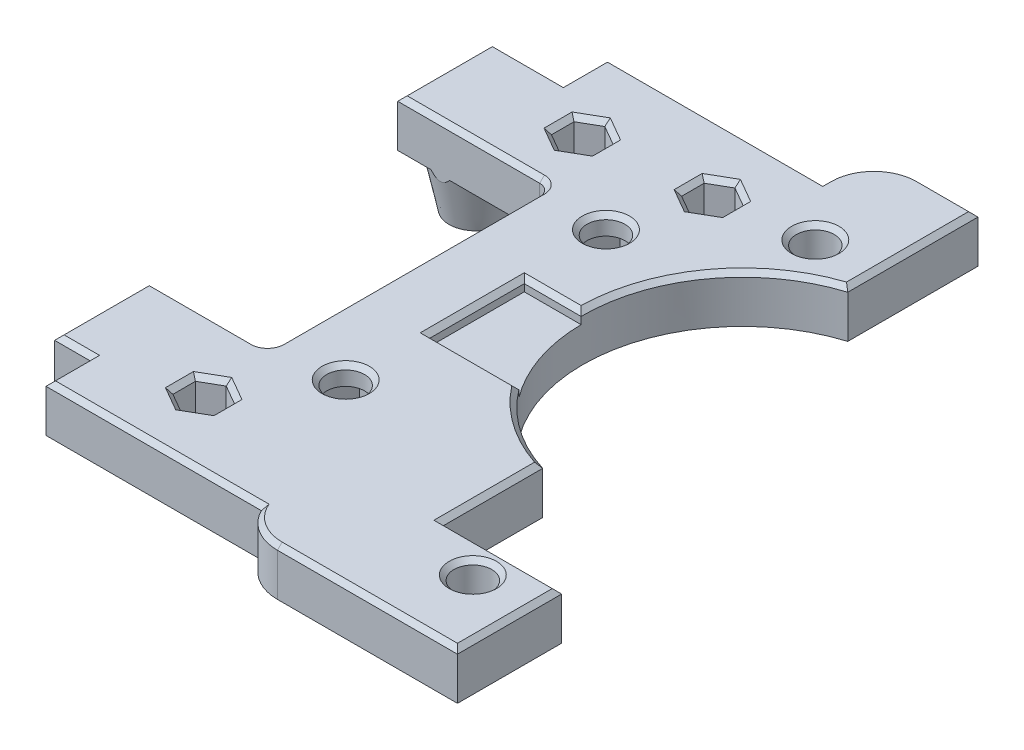
SolidWorks part; units mm, degrees
ref_plane "前视基准面" through (0, 0, 0) normal (0, 0, 1) x (1, 0, 0)
ref_plane "上视基准面" through (0, 0, 0) normal (0, 1, 0) x (1, 0, 0)
ref_plane "右视基准面" through (0, 0, 0) normal (1, 0, 0) x (0, 0, -1)
other "Configuration Table"
sketch "草图1" plane through (0, 0, 0) normal (0, 1, 0) x (1, 0, 0)
  line L1 (0, 0) -> (20, 0)
  line L2 (0, 0) -> (0, 35.74)
  line L3 (0, 35.74) -> (20, 35.74)
  line L4 (20, 0) -> (20, 35.74)
  dimension "D1" = 35.74
  dimension "D2" = 20
extrude "凸台-拉伸1" add sketch "草图1" along normal blind 4
sketch "草图2" plane through (0, 0, 0) normal (0, -1, 0) x (1, 0, 0)
  line L0 (20, 0) -> (20, -35.74) construction
  line L1 (20, 0) -> (11.2, 0)
  line L2 (20, 0) -> (20, 8.08)
  line L3 (20, 8.08) -> (11.2, 8.08)
  line L4 (11.2, 0) -> (11.2, 8.08)
  line L5 (20, -35.74) -> (0, -35.74) construction
  line L6 (20, -35.74) -> (11.2, -35.74)
  line L7 (20, -35.74) -> (20, -45.92)
  line L8 (20, -45.92) -> (11.2, -45.92)
  line L9 (11.2, -35.74) -> (11.2, -45.92)
  line L10 (0, 0) -> (20, 0) construction
  dimension "D1" = 8.8
  dimension "D2" = 8.8
  dimension "D3" = 8.08
  dimension "D4" = 0
  dimension "D5" = 10.18
extrude "凸台-拉伸2" add sketch "草图2" against normal blind 4
sketch "草图3" plane through (0, 0, 0) normal (0, -1, 0) x (-1, 0, 0)
  line L0 (-20, -8.08) -> (-11.2, -8.08) construction
  line L1 (-20, -8.08) -> (-20, 45.92) construction
  circle A0 centre (-24, 22.02) radius 13.5
  dimension "D3" = 27
  dimension "D1" = 30.1
  dimension "D2" = 4
extrude "切除-拉伸1" cut sketch "草图3" against normal blind 10
sketch "草图4" plane through (0, 0, 0) normal (0, -1, 0) x (-1, 0, 0)
  line L1 (-18, 2.17) -> (-9, 2.17)
  line L2 (-18, 2.17) -> (-18, -2.83)
  line L3 (-18, -2.83) -> (-9, -2.83)
  line L4 (-9, 2.17) -> (-9, -2.83)
  line L7 (-20, -8.08) -> (-11.2, -8.08) construction
  line L8 (-20, -8.08) -> (-20, 9.1262) construction
  dimension "D1" = 5
  dimension "D2" = 9
  dimension "D3" = 5.25
  dimension "D4" = 2
extrude "切除-拉伸2" cut sketch "草图4" against normal blind 1
sketch "草图5" plane through (20, 0, 0) normal (1, 0, 0) x (0, 0, -1)
  line L0 (-8.08, 4) -> (-8.08, 0) construction
  line L1 (-8.08, 0) -> (0.729, 0)
  line L2 (-8.08, 0) -> (-8.08, 4)
  line L3 (-8.08, 4) -> (0.729, 4)
  line L4 (0.729, 0) -> (0.729, 4)
  line L5 (-8.08, 0) -> (9.1262, 0) construction
  line L6 (-8.08, 4) -> (9.1262, 4) construction
extrude "凸台-拉伸3" add sketch "草图5" along normal blind 10
sketch "草图6" plane through (0, 0, 0) normal (0, -1, 0) x (-1, 0, 0)
  line L0 (-11.2, 35.74) -> (-11.2, 45.92) construction
  line L1 (-11.2, 45.92) -> (-20, 45.92) construction
  line L2 (-30, -8.08) -> (-11.2, -8.08) construction
  line L3 (-11.2, -8.08) -> (-11.2, -2.83) construction
  circle A0 centre (-15.2, 36.97) radius 1.6
  circle A1 centre (-25.25, -2.03) radius 1.6
  dimension "D1" = 4
  dimension "D2" = 8.95
  dimension "D3" = 3.2
  dimension "D4" = 6.05
  dimension "D5" = 14.05
  dimension "D6" = 3.2
extrude "切除-拉伸3" cut sketch "草图6" against normal blind 10
sketch "草图7" plane through (0, 0, 0) normal (0, -1, 0) x (-1, 0, 0)
  line L0 (0, 35.74) -> (0, 0) construction
  line L1 (-11.2, 35.74) -> (0, 35.74) construction
  circle A0 centre (-5.6, 28.87) radius 1.6
  circle A1 centre (-5.6, 6.87) radius 1.6
  point P6 (0, 17.87)
  point P9 (-5.6, 35.74)
  dimension "D1" = 3.2
  dimension "D2" = 3.2
  dimension "D3" = 11
  dimension "D4" = 11
  dimension "D5" = 0
  dimension "D6" = 0
extrude "切除-拉伸4" cut sketch "草图7" against normal through all
sketch "草图8" plane through (0, 0, 0) normal (0, -1, 0) x (1, 0, 0)
  line L0 (11.2, -35.74) -> (11.2, -45.92) construction
  line L1 (0, -35.74) -> (11.2, -35.74)
  line L2 (0, -35.74) -> (0, -39.74)
  line L3 (0, -39.74) -> (11.2, -39.74)
  line L4 (11.2, -35.74) -> (11.2, -39.74)
  line L5 (11.2, 8.08) -> (11.2, 2.83) construction
  line L6 (0, 0) -> (11.2, 0)
  line L7 (0, 0) -> (0, 4)
  line L8 (0, 4) -> (11.2, 4)
  line L9 (11.2, 0) -> (11.2, 4)
  dimension "D1" = 4
  dimension "D2" = 4
extrude "凸台-拉伸4" add sketch "草图8" against normal up to surface (4 mm away) up to face at (5.6, 4, -30.47)
sketch "草图9" plane through (0, 0, 0) normal (0, -1, 0) x (-1, 0, 0)
  circle A0 centre (-7.6, 35.87) radius 1.65
  circle A1 centre (-0.6, -0.13) radius 1.65
  circle A2 centre (-5.6, 6.87) radius 1.6 construction
  circle A3 centre (-5.6, 28.87) radius 1.6 construction
  dimension "D1" = 3.3
  dimension "D2" = 3.3
  dimension "D3" = 7
  dimension "D4" = 7
  dimension "D5" = 2
  dimension "D6" = 5
extrude "切除-拉伸5" cut sketch "草图9" against normal through all
sketch "草图10" plane through (0, 0, 0) normal (-1, 0, 0) x (0, 0, 1)
  line L0 (-39.74, 0) -> (-45.92, 0) construction
  line L1 (-39.74, 0) -> (-29.87, 0)
  line L2 (-39.74, 0) -> (-39.74, 4)
  line L3 (-39.74, 4) -> (-29.87, 4)
  line L4 (-29.87, 0) -> (-29.87, 4)
  line L5 (-39.74, 4) -> (-39.74, 0) construction
  line L6 (-39.74, 4) -> (-1.407, 4) construction
  line L7 (-39.74, 0) -> (-1.407, 0) construction
  line L8 (4, 4) -> (-5.87, 4)
  line L9 (4, 4) -> (4, 0)
  line L10 (4, 0) -> (-5.87, 0)
  line L11 (-5.87, 4) -> (-5.87, 0)
  dimension "D1" = 9.87
  dimension "D2" = 9.87
extrude "凸台-拉伸5" add sketch "草图10" along normal blind 7
sketch "草图11" plane through (0, 0, 0) normal (0, -1, 0) x (-1, 0, 0)
  circle A0 centre (2.4, 34.87) radius 1.65
  circle A1 centre (-7.6, 35.87) radius 1.65 construction
  dimension "D1" = 3.3
  dimension "D2" = 10
  dimension "D3" = 1
extrude "切除-拉伸6" cut sketch "草图11" against normal blind 8
sketch "草图12" plane through (0, 0, 0) normal (0, -1, 0) x (-1, 0, 0)
  line L1 (-11.2, -2.83) -> (-4.6, -2.83)
  line L2 (-11.2, -2.83) -> (-11.2, 1.75)
  line L3 (-11.2, 1.75) -> (-4.6, 1.75)
  line L4 (-4.6, -2.83) -> (-4.6, 1.75)
  dimension "D1" = 6.6
extrude "切除-拉伸7" cut sketch "草图12" against normal up to surface (1 mm away) up to face at (12.7333, 1, 0.22)
sketch "草图13" plane through (0, 0, 0) normal (0, -1, 0) x (-1, 0, 0)
  circle A0 centre (-0.6, -0.13) radius 1.65
  arc A1 (0, 1.407) -> (0, -1.667) centre (-0.6, -0.13) ccw construction
  dimension "D1" = 0
extrude "切除-拉伸8" cut sketch "草图13" against normal blind 5
sketch "草图14" plane through (0, 0, 0) normal (0, -1, 0) x (-1, 0, 0)
  line L0 (-11.2, -8.08) -> (-11.2, -4) construction
  line L1 (7, -4) -> (-11.2, -4)
  line L2 (7, -4) -> (7, -5.86)
  line L3 (7, -5.86) -> (-11.2, -5.86)
  line L4 (-11.2, -4) -> (-11.2, -5.86)
  line L5 (-11.2, 39.74) -> (-11.2, 45.92) construction
  line L6 (7, 39.74) -> (-11.2, 39.74)
  line L7 (7, 39.74) -> (7, 41.6)
  line L8 (7, 41.6) -> (-11.2, 41.6)
  line L9 (-11.2, 39.74) -> (-11.2, 41.6)
  dimension "D1" = 1.86
  dimension "D2" = 1.86
extrude "凸台-拉伸6" add sketch "草图14" against normal up to surface (4 mm away) up to face at (-2.4, 4, -36.52)
sketch "草图16" plane through (0, 4, 0) normal (0, 1, 0) x (1, 0, 0)
  line L0 (0, 29.87) -> (0, 5.87) construction
  line L1 (5.7, 13.87) -> (15.7, 13.87)
  line L2 (5.7, 13.87) -> (5.7, 21.87)
  line L3 (5.7, 21.87) -> (15.7, 21.87)
  line L4 (15.7, 13.87) -> (15.7, 21.87)
  point P4 (5.7, 17.87)
  point P7 (0, 17.87)
  dimension "D1" = 8
  dimension "D2" = 0
  dimension "D3" = 10
  dimension "D4" = 5.7
extrude "切除-拉伸9" cut sketch "草图16" against normal blind 1
sketch "草图17" plane through (0, 0, 0) normal (0, -1, 0) x (-1, 0, 0)
  line L1 (-8.8332, 28.87) -> (-7.2166, 26.07)
  line L2 (-7.2166, 26.07) -> (-3.9834, 26.07)
  line L3 (-3.9834, 26.07) -> (-2.3668, 28.87)
  line L4 (-2.3668, 28.87) -> (-3.9834, 31.67)
  line L5 (-3.9834, 31.67) -> (-7.2166, 31.67)
  line L6 (-7.2166, 31.67) -> (-8.8332, 28.87)
  line L7 (-8.8332, 6.87) -> (-7.2166, 4.07)
  line L8 (-7.2166, 4.07) -> (-3.9834, 4.07)
  line L9 (-3.9834, 4.07) -> (-2.3668, 6.87)
  line L10 (-2.3668, 6.87) -> (-3.9834, 9.67)
  line L11 (-3.9834, 9.67) -> (-7.2166, 9.67)
  line L12 (-7.2166, 9.67) -> (-8.8332, 6.87)
  circle A0 centre (-5.6, 28.87) radius 2.8 construction
  circle A1 centre (-5.6, 6.87) radius 2.8 construction
  dimension "D1" = 5.6
  dimension "D2" = 5.6
extrude "切除-拉伸10" cut sketch "草图17" against normal blind 2.4
fillet "圆角1" radius 4 2 edges at (11.2, 2, 8.08) (11.2, 2, -45.92)
sketch "草图19" plane through (0, 4, 0) normal (0, 1, 0) x (1, 0, 0)
  line L1 (0.6, -2.0353) -> (2.25, -1.0826)
  line L2 (2.25, -1.0826) -> (2.25, 0.8226)
  line L3 (2.25, 0.8226) -> (0.6, 1.7753)
  line L4 (0.6, 1.7753) -> (-1.05, 0.8226)
  line L5 (-1.05, 0.8226) -> (-1.05, -1.0826)
  line L6 (-1.05, -1.0826) -> (0.6, -2.0353)
  line L7 (-2.4, 32.9647) -> (-0.75, 33.9174)
  line L8 (-0.75, 33.9174) -> (-0.75, 35.8226)
  line L9 (-0.75, 35.8226) -> (-2.4, 36.7753)
  line L10 (-2.4, 36.7753) -> (-4.05, 35.8226)
  line L11 (-4.05, 35.8226) -> (-4.05, 33.9174)
  line L12 (-4.05, 33.9174) -> (-2.4, 32.9647)
  line L13 (7.6, 33.9647) -> (9.25, 34.9174)
  line L14 (9.25, 34.9174) -> (9.25, 36.8226)
  line L15 (9.25, 36.8226) -> (7.6, 37.7753)
  line L16 (7.6, 37.7753) -> (5.95, 36.8226)
  line L17 (5.95, 36.8226) -> (5.95, 34.9174)
  line L18 (5.95, 34.9174) -> (7.6, 33.9647)
  circle A0 centre (0.6, -0.13) radius 1.65 construction
  circle A1 centre (-2.4, 34.87) radius 1.65 construction
  circle A2 centre (7.6, 35.87) radius 1.65 construction
  circle A4 centre (0.6, -0.13) radius 1.65 construction
  circle A5 centre (-2.4, 34.87) radius 1.65 construction
  circle A6 centre (7.6, 35.87) radius 1.65 construction
  dimension "D1" = 0
  dimension "D2" = 0
  dimension "D3" = 0
extrude "切除-拉伸11" cut sketch "草图19" against normal through all
fillet "圆角2" radius 1 2 edges at (0, 2, -5.87) (0, 2, -29.87)
sketch "草图20" plane through (0, 4, 0) normal (0, 1, 0) x (1, 0, 0)
  line L0 (-7, 29.87) -> (-7, 41.6) construction
  line L1 (-7, 37.87) -> (-13, 37.87)
  line L2 (-7, 37.87) -> (-7, 29.87)
  line L3 (-7, 29.87) -> (-13, 29.87)
  line L4 (-13, 37.87) -> (-13, 29.87)
  line L5 (-7, -5.86) -> (-7, 5.87) construction
  line L6 (-7, -2.13) -> (-10, -2.13)
  line L7 (-7, -2.13) -> (-7, 5.87)
  line L8 (-7, 5.87) -> (-10, 5.87)
  line L9 (-10, -2.13) -> (-10, 5.87)
  line L10 (-7, 29.87) -> (-1, 29.87) construction
  line L11 (-7, 5.87) -> (-1, 5.87) construction
  dimension "D1" = 0
  dimension "D2" = 0
  dimension "D3" = 8
  dimension "D4" = 8
  dimension "D5" = 3
  dimension "D6" = 6
extrude "凸台-拉伸7" add sketch "草图20" against normal up to surface (4 mm away) up to face at (0.6, 0, 0.13)
sketch "草图21" plane through (0, 0, 0) normal (0, -1, 0) x (-1, 0, 0)
  line L0 (4.05, 35.8226) -> (4.05, 33.9174) construction
  line L1 (1.05, 0.8226) -> (1.05, -1.0826) construction
  circle A0 centre (6.4, 2.87) radius 2.1
  circle A1 centre (9.4, 32.87) radius 2.1
  point P8 (4.05, 34.87)
  point P11 (1.05, -0.13)
  dimension "D1" = 7
  dimension "D2" = 7
  dimension "D4" = 3
  dimension "D5" = 4.2
  dimension "D6" = 4.2
  dimension "D3" = 2
extrude "凸台-拉伸8" add sketch "草图21" along normal blind 4
chamfer "倒角2" distance 1 angle 78 2 edges at (-9.4, 0, -34.97) (-6.4, 0, -4.97) first distance on face at (-9.4, 0, -34.97)
chamfer "倒角1" distance 0.4 angle 45 49 edges at (25.25, 4, 0.43) (15.2, 4, -38.57) (5.6, 4, -8.47) (5.6, 4, -30.47) (-7, 4, 3.995) (-5.5, 4, -5.87) (0, 4, -17.87) (-7, 4, -29.87) (-7, 4, -39.735) (2.1, 4, -41.6) (11.2, 4, -41.76) (12.3716, 4, -44.7484) (17.6, 4, -45.92) (20, 4, -40.4169) (16.2471, 4, -10.9682) (13.0871, 4, -29.9673) (20, 4, -4.9276) (25, 4, -0.729) (30, 4, 3.6755) (22.3911, 4, 8.08) (12.675, 4, 7.48) (2.1, 4, 5.86) (8.1004, 4, -21.87) (5.7, 4, -17.87) (9.4688, 4, -13.87) (9.25, 4, -35.87) (8.425, 4, -37.2989) (6.775, 4, -37.2989) (5.95, 4, -35.87) (6.775, 4, -34.4411) (8.425, 4, -34.4411) (-0.75, 4, -34.87) (-1.575, 4, -36.2989) (-3.225, 4, -36.2989) (-4.05, 4, -34.87) (-3.225, 4, -33.4411) (-1.575, 4, -33.4411) (2.25, 4, 0.13) (1.425, 4, -1.2989) (-0.225, 4, -1.2989) (-1.05, 4, 0.13) (-0.225, 4, 1.5589) (1.425, 4, 1.5589) (-0.2929, 4, -6.1629) (-0.2929, 4, -29.5771) (-8.5, 4, 2.13) (-10, 4, -1.87) (-13, 4, -33.87) (-10, 4, -37.87)
